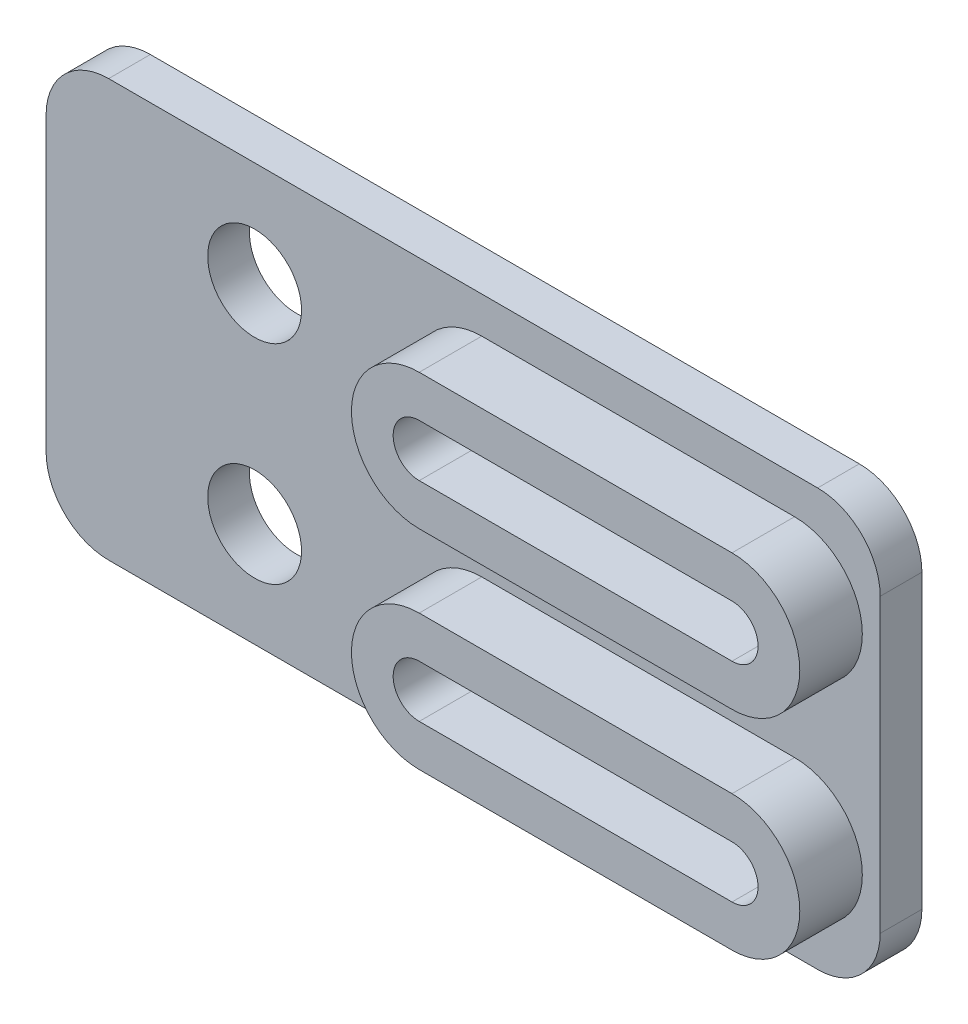
SolidWorks part; units mm, degrees
ref_plane "Płaszczyzna przednia" through (0, 0, 0) normal (0, 0, 1) x (1, 0, 0)
ref_plane "Płaszczyzna górna" through (0, 0, 0) normal (0, 1, 0) x (1, 0, 0)
ref_plane "Płaszczyzna prawa" through (0, 0, 0) normal (1, 0, 0) x (0, 0, -1)
sketch "Szkic1" plane through (0, 0, 0) normal (0, 0, 1) x (1, 0, 0)
  line L0 (1.3876, -4.7136) -> (16.3876, -4.7136) construction
  line L1 (-19.5054, 10.2864) -> (20.4946, 10.2864)
  line L2 (-19.5054, 10.2864) -> (-19.5054, -9.7136)
  line L3 (-19.5054, -9.7136) -> (20.4946, -9.7136)
  line L4 (20.4946, 10.2864) -> (20.4946, -9.7136)
  line L5 (1.3876, -3.4636) -> (16.3876, -3.4636)
  line L6 (1.3876, -5.9636) -> (16.3876, -5.9636)
  line L7 (1.3876, -4.7136) -> (16.3876, -4.7136) construction
  line L8 (1.3876, -1.4636) -> (16.3876, -1.4636)
  line L9 (1.3876, -7.9636) -> (16.3876, -7.9636)
  line L10 (1.3876, 5.2864) -> (16.3876, 5.2864) construction
  line L11 (1.3876, 6.5364) -> (16.3876, 6.5364)
  line L12 (1.3876, 4.0364) -> (16.3876, 4.0364)
  line L13 (1.3876, 5.2864) -> (16.3876, 5.2864) construction
  line L14 (1.3876, 8.5364) -> (16.3876, 8.5364)
  line L15 (1.3876, 2.0364) -> (16.3876, 2.0364)
  circle A0 centre (-9.5054, 5.2864) radius 2.25
  circle A1 centre (-9.5054, -4.7136) radius 2.25
  arc A2 (1.3876, -3.4636) -> (1.3876, -5.9636) centre (1.3876, -4.7136) ccw
  arc A3 (16.3876, -5.9636) -> (16.3876, -3.4636) centre (16.3876, -4.7136) ccw
  arc A4 (1.3876, -1.4636) -> (1.3876, -7.9636) centre (1.3876, -4.7136) ccw
  arc A5 (16.3876, -7.9636) -> (16.3876, -1.4636) centre (16.3876, -4.7136) ccw
  arc A6 (1.3876, 6.5364) -> (1.3876, 4.0364) centre (1.3876, 5.2864) ccw
  arc A7 (16.3876, 4.0364) -> (16.3876, 6.5364) centre (16.3876, 5.2864) ccw
  arc A8 (1.3876, 8.5364) -> (1.3876, 2.0364) centre (1.3876, 5.2864) ccw
  arc A9 (16.3876, 2.0364) -> (16.3876, 8.5364) centre (16.3876, 5.2864) ccw
  point P10 (8.8876, -4.7136)
  point P15 (8.8876, -4.7136)
  point P24 (8.8876, 5.2864)
  point P29 (8.8876, 5.2864)
  dimension "D3" = 4.5
  dimension "D6" = 4.5
  dimension "D1" = 40
  dimension "D2" = 20
  dimension "D4" = 10
  dimension "D5" = 5
  dimension "D7" = 10
  dimension "D8" = 5
  dimension "D9" = 2.5
  dimension "D10" = 2
  dimension "D11" = 15
  dimension "D12" = 5
  dimension "D13" = 2.5
  dimension "D14" = 2
extrude "Dodanie-wyciągnięcie1" add sketch "Szkic1" along normal blind 2 contours L4 L1 L2 L3 A9 L15 A8 L14 A5 L9 A4 L8 A1 A0 region at (-3.206, 0.2864, 0)
extrude "Dodanie-wyciągnięcie2" add sketch "Szkic1<3>" along normal blind 5 contours L9 A5 L8 A4 A3 L6 A2 L5 | L15 A9 L14 A8 | L12 A7 L11 A6 region at (8.8876, -1.6882, 0)
sketch "Szkic1<3>" plane through (0, 0, 0) normal (0, 0, 1) x (1, 0, 0) same geometry as "Szkic1"
fillet "Zaokrąglenie1" radius 3 4 edges at (-19.5054, -9.7136, 1) (20.4946, -9.7136, 1) (20.4946, 10.2864, 1) (-19.5054, 10.2864, 1)
